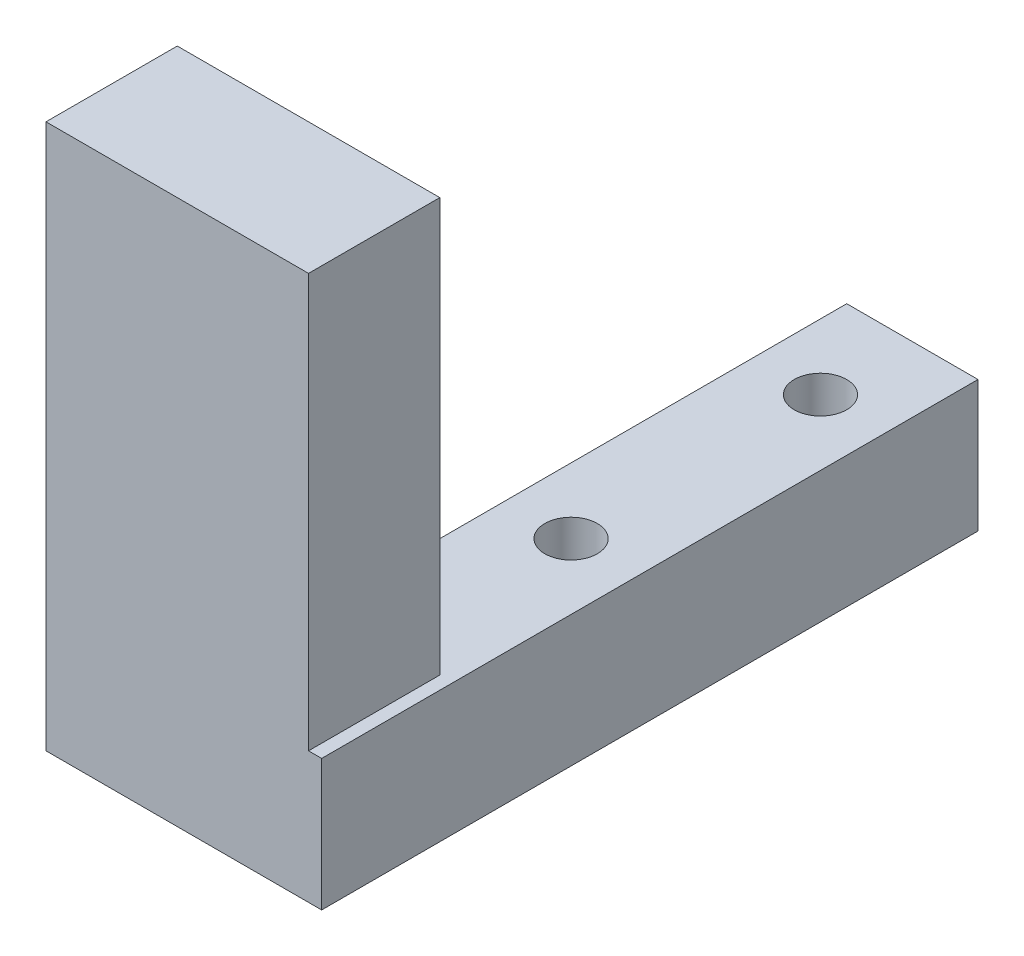
SolidWorks part; units mm, degrees
ref_plane "Front Plane" through (0, 0, 0) normal (0, 0, 1) x (1, 0, 0)
ref_plane "Top Plane" through (0, 0, 0) normal (0, 1, 0) x (1, 0, 0)
ref_plane "Right Plane" through (0, 0, 0) normal (1, 0, 0) x (0, 0, -1)
sketch "Sketch1" plane through (0, 0, 0) normal (0, 0, 1) x (1, 0, 0)
  line L1 (-7.8513, 3.6433) -> (2.1487, 3.6433)
  line L2 (-7.8513, 3.6433) -> (-7.8513, -6.3567)
  line L3 (-7.8513, -6.3567) -> (2.1487, -6.3567)
  line L4 (2.1487, 3.6433) -> (2.1487, -6.3567)
  dimension "D1" = 10
  dimension "D2" = 10
extrude "Boss-Extrude1" add sketch "Sketch1" along normal blind 50
sketch "Sketch3" plane through (-7.8513, 0, 0) normal (-1, 0, 0) x (0, 0, 1)
  line L0 (50, -6.3567) -> (0, -6.3567) construction
  line L1 (50, 3.6433) -> (40, 3.6433)
  line L2 (50, 3.6433) -> (50, -6.3567)
  line L3 (50, -6.3567) -> (40, -6.3567)
  line L4 (40, 3.6433) -> (40, -6.3567)
  dimension "D1" = 10
  dimension "D2" = 10
extrude "Boss-Extrude3" add sketch "Sketch3" along normal blind 11
sketch "Sketch8" plane through (0, 3.6433, 0) normal (0, 1, 0) x (1, 0, 0)
  line L1 (-18.8513, -50) -> (1.1487, -50)
  line L2 (-18.8513, -50) -> (-18.8513, -40)
  line L3 (-18.8513, -40) -> (1.1487, -40)
  line L4 (1.1487, -50) -> (1.1487, -40)
  dimension "D1" = 20
extrude "Boss-Extrude4" add sketch "Sketch8" along normal blind 23
sketch "Sketch9" plane through (0, 3.6433, 0) normal (0, 1, 0) x (1, 0, 0)
  line L0 (-2.8513, 0) -> (-2.8513, -5)
  line L3 (2.1487, 0) -> (-7.8513, 0) construction
  line L4 (-2.8513, -5) -> (-2.8513, -7)
  line L5 (-2.8513, -9) -> (-2.8513, -24)
  line L6 (-2.8513, -24) -> (-2.8513, -26)
  line L7 (2.1487, -50) -> (2.1487, 0) construction
  circle A0 centre (-2.8513, -7) radius 2
  circle A1 centre (-2.8513, -26) radius 2
  dimension "D1" = 5
  dimension "D3" = 15
  dimension "D2" = 2
  dimension "D4" = 2
extrude "Cut-Extrude2" cut sketch "Sketch9" against normal blind 23 contours A0
extrude "Cut-Extrude3" cut sketch "Sketch9<4>" against normal blind 23 contours A1
sketch "Sketch9<4>" plane through (0, 3.6433, 0) normal (0, 1, 0) x (1, 0, 0) same geometry as "Sketch9"
extrude "Boss-Extrude5" add sketch "Sketch8<4>" along normal blind 31
sketch "Sketch8<4>" plane through (0, 3.6433, 0) normal (0, 1, 0) x (1, 0, 0) same geometry as "Sketch8"
extrude "Boss-Extrude6" add sketch "Sketch8<5>" along normal blind 31.5
sketch "Sketch8<5>" plane through (0, 3.6433, 0) normal (0, 1, 0) x (1, 0, 0) same geometry as "Sketch8"
